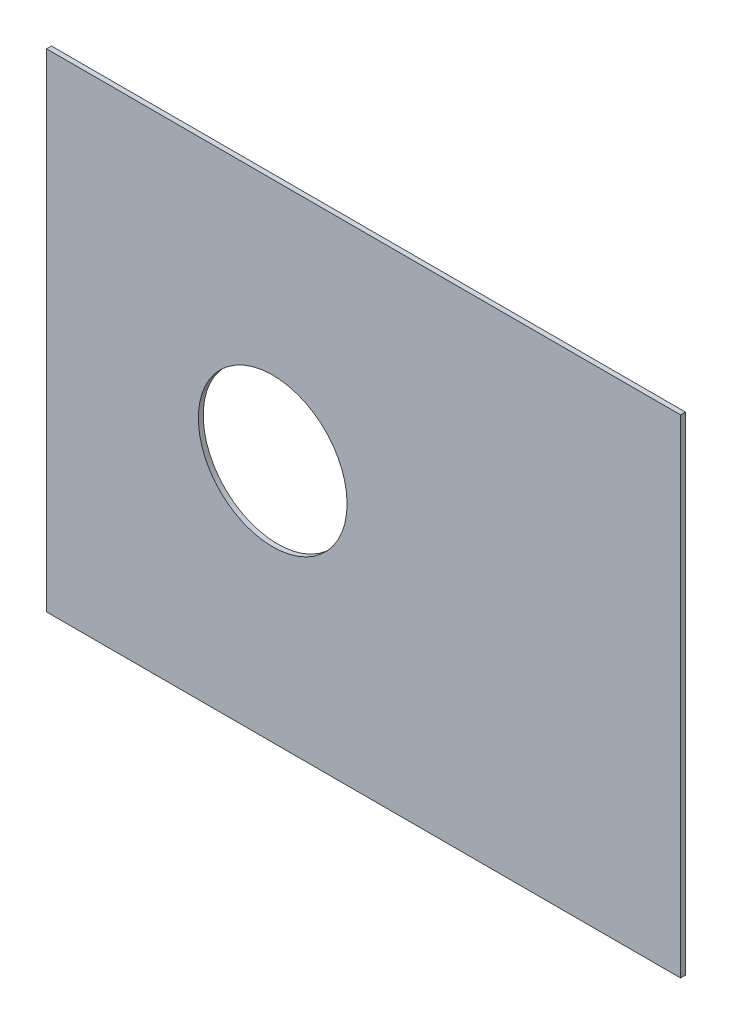
SolidWorks part; units mm, degrees
ref_plane "Спереди" through (0, 0, 0) normal (0, 0, 1) x (1, 0, 0)
ref_plane "Сверху" through (0, 0, 0) normal (0, 1, 0) x (1, 0, 0)
ref_plane "Справа" through (0, 0, 0) normal (1, 0, 0) x (0, 0, -1)
other "Configuration Table"
sketch "Эскиз1" plane through (0, 0, 0) normal (0, 0, 1) x (1, 0, 0)
  line L1 (130, 100) -> (-130, 100)
  line L2 (130, 100) -> (130, -100)
  line L3 (130, -100) -> (-130, -100)
  line L4 (-130, 100) -> (-130, -100)
  line L5 (130, 100) -> (-130, -100) construction
  line L6 (130, -100) -> (-130, 100) construction
  circle A0 centre (-37.26, 0) radius 30.5
  point P0 (0, 0)
  dimension "D3" = 61
  dimension "D1" = 260
  dimension "D2" = 200
  dimension "D4" = 92.74
extrude "Бобышка-Вытянуть1" add sketch "Эскиз1" along normal blind 2
